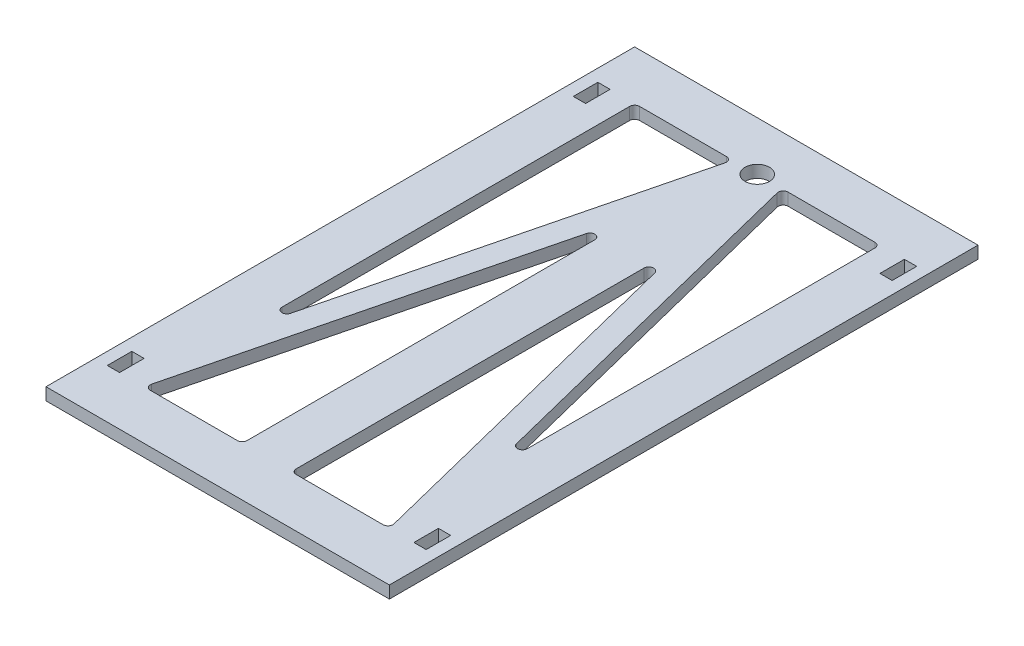
SolidWorks part; units mm, degrees
material "Beech"
ref_plane "Front Plane" through (0, 0, 0) normal (0, 0, 1) x (1, 0, 0)
ref_plane "Top Plane" through (0, 0, 0) normal (0, 1, 0) x (1, 0, 0)
ref_plane "Right Plane" through (0, 0, 0) normal (1, 0, 0) x (0, 0, -1)
sketch "Sketch1" plane through (0, 0, 0) normal (0, 1, 0) x (1, 0, 0)
  line L0 (0, 0) -> (177.8, 0)
  line L1 (0, 0) -> (0, 304.8)
  line L2 (177.8, 0) -> (177.8, 304.8)
  line L3 (0, 304.8) -> (177.8, 304.8)
  line L4 (0, 0) -> (12.7, 0)
  line L5 (0, 0) -> (0, -6.35)
  line L8 (177.8, 0) -> (165.1, 0)
  line L12 (127, 0) -> (114.3, 0)
  line L16 (50.8, 0) -> (63.5, 0)
  line L20 (165.1, 279.4) -> (171.45, 279.4)
  line L21 (165.1, 279.4) -> (165.1, 266.7)
  line L22 (171.45, 279.4) -> (171.45, 266.7)
  line L23 (165.1, 266.7) -> (171.45, 266.7)
  line L24 (6.35, 279.4) -> (12.7, 279.4)
  line L25 (6.35, 279.4) -> (6.35, 266.7)
  line L26 (12.7, 279.4) -> (12.7, 266.7)
  line L27 (6.35, 266.7) -> (12.7, 266.7)
  line L28 (6.35, 38.1) -> (12.7, 38.1)
  line L29 (6.35, 38.1) -> (6.35, 25.4)
  line L30 (12.7, 38.1) -> (12.7, 25.4)
  line L31 (6.35, 25.4) -> (12.7, 25.4)
  line L32 (165.1, 38.1) -> (171.45, 38.1)
  line L33 (165.1, 38.1) -> (165.1, 25.4)
  line L34 (171.45, 38.1) -> (171.45, 25.4)
  line L35 (165.1, 25.4) -> (171.45, 25.4)
  line L36 (101.6, 279.4) -> (152.4, 279.4)
  line L37 (152.4, 279.4) -> (152.4, 76.2)
  line L38 (152.4, 76.2) -> (101.6, 279.4)
  line L39 (101.6, 228.6) -> (101.6, 25.4)
  line L40 (101.6, 25.4) -> (152.4, 25.4)
  line L41 (152.4, 25.4) -> (101.6, 228.6)
  line L42 (76.2, 279.4) -> (25.4, 279.4)
  line L43 (25.4, 279.4) -> (25.4, 76.2)
  line L44 (25.4, 76.2) -> (76.2, 279.4)
  line L45 (76.2, 228.6) -> (76.2, 25.4)
  line L46 (76.2, 25.4) -> (25.4, 25.4)
  line L47 (25.4, 25.4) -> (76.2, 228.6)
  circle A0 centre (88.9, 279.4) radius 6.35
  point P21 (88.9, 304.8)
  dimension "D8" = 12.7
  dimension "D1" = 177.8
  dimension "D6" = 304.8
  dimension "D7" = 25.4
  dimension "D9" = 25.4
  dimension "D10" = 25.4
  dimension "D11" = 12.7
  dimension "D12" = 12.7
  dimension "D13" = 203.2
  dimension "D14" = 50.8
  dimension "D15" = 50.8
extrude "Front Panel" add sketch "Sketch1" along normal blind 6.35 contours L3 L1 L0 L2 A0 L35 L33 L32 L34 L31 L29 L28 L30 L27 L25 L24 L26 L23 L21 L20 L22 | L5 L0 | L0 | L0 | L0 region at (88.9, 0, -151.9139)
fillet "Fillet1" radius 2.54 12 edges at (25.4, 3.175, -76.2) (152.4, 3.175, -76.2) (25.4, 3.175, -25.4) (76.2, 3.175, -25.4) (101.6, 3.175, -25.4) (152.4, 3.175, -25.4) (76.2, 3.175, -228.6) (101.6, 3.175, -228.6) (25.4, 3.175, -279.4) (76.2, 3.175, -279.4) (101.6, 3.175, -279.4) (152.4, 3.175, -279.4)
equation "\"CageLeftBottomEdge\"=22.11mm"
equation "\"CageLeftTopEdge\"=22.11mm"
equation "\"CageRightBottomEdge\"=21.63mm"
equation "\"CageRightTopEdge\"=21.63mm"
equation "\"CageHeight\"=86.04mm"
equation "\"CageLength\"=73.76mm"
equation "\"CageTopScrewClearance\"=10mm"
equation "\"CageBottomScrewClearance\"=25mm"
equation "\"CageLeftTopDepth\"= 11.65mm"
equation "\"CageLeftBottomDepth\"=11.11mm"
equation "\"CageLeftTopHeight\"=8.56175mm"
equation "\"CageLeftBottomHeight\"=16mm"
equation "\"CageRightTopDepth\"= 11.05mm"
equation "\"CageRightBottomDepth\"=10.58mm"
equation "\"CageRightTopHeight\"=9.6mm"
equation "\"CageRightBottomHeight\"=15.49mm"
equation "\"CageLeftTopChannelDepth\"=2.41908mm"
equation "\"CageLeftBottomChannelDepth\"=2.588mm"
equation "\"CageLeftChannelHeight\"=11.7mm"
equation "\"CageRightTopChannelDepth\"=2.32mm"
equation "\"CageRightBottomChannelDepth\"=2.318mm"
equation "\"CageRightChannelHeight\"=10mm"
equation "\"CageChanRelHeight\"=23.99mm"
equation "\"CageChanRelDepth\"=5.492mm"
equation "\"CageChamberRadius\"=16.261mm"
equation "\"CageScrewDiameter\"=4.8mm"
equation "\"CageSetScrewDiameter\"=3.5mm"
equation "\"CageAxleRadius\"=6.639mm"
equation "\"CageAxleKeyHeight\"=1.619mm"
equation "\"CageAxleKeyWidth\"=2.662mm"
equation "\"CageHoseWindowWidth\"=16.29mm"
equation "\"CageHoseWindowHeight\"=26.5mm"
equation "\"CageHoseWindow-Edge\"=8.89mm"
equation "\"CageScrew-VerticalEdge\"=5.0mm"
equation "\"CageScrew-HorizontalEdge\"=7.5mm"
equation "\"CageScrew-HoseCornerScrewEdge\"=4.45mm"
equation "\"CageAxle-BottomEdge\"=56.05mm"
equation "\"CageAxle-FrontEdge\"=46.03mm"
equation "\"CageBackSetScrew-Axle\"=40mm"
equation "\"CageFrontSetScrew-Axle\"=22mm"
equation "\"CageVelocityWindow-BackEdge\"=34.8mm"
equation "\"CageVelocityWindow-BottomEdge\"=27.55mm"
equation "\"CageVelocityWindowHeight\"=22.29mm"
equation "\"CageVelocityWindowWidth\"=12.61mm"
equation "\"TriggerSlot-BottomEdge\"=6.35mm"
equation "\"TriggerSlot-FrontEdge\"=15mm"
equation "\"TriggerSlotSize\"=6.7mm"
equation "\"TriggerRackOffset\"=6mm"
equation "\"TriggerSlotSizeInt\"=.25in"
equation "\"MotorMountLegLength\"=.25in"
equation "\"GearOffset\"=.264907in"
equation "\"TriggerSlotSpacing\"=.25in"
equation "\"TriggerMiniSlotWidth\"=3.5mm"
equation "\"TriggerRackWidth\"=6.5mm"
equation "\"pandiscradius\"=14in"
equation "\"towermaterialwidth\"=.25in"
equation "\"towerslotlength\"=.5in"
equation "\"towermarkerspace\"=5in"
equation "\"towerslothorizoffset\"=1in"
equation "\"towerslothorizspacing\"=2in"
equation "\"towerslotvertoffset\"=3in"
equation "\"towerslotvertspacing\"=1in"
equation "\"towerheight\"=12in"
equation "\"towerupslot\"=1in"
equation "\"D1@Sketch1\"=(\"towerslothorizoffset\"+\"towerslothorizspacing\"+\"towerslotlength\")*2"
equation "\"D2@Sketch1\"=\"towermaterialwidth\""
equation "\"D3@Sketch1\"=\"towerslotlength\""
equation "\"D4@Sketch1\"=\"towerslothorizspacing\""
equation "\"D5@Sketch1\"=\"towerslothorizspacing\""
equation "\"D6@Sketch1\"=\"towerheight\""
equation "\"D7@Sketch1\"=\"towerupslot\""
equation "\"toweraxle\"=.5in"
equation "\"D8@Sketch1\"=\"toweraxle\""
equation "\"D9@Sketch1\"=\"towerupslot\""
equation "\"D10@Sketch1\"= \"towerupslot\""
equation "\"D1@Front Panel\"=\"towermaterialwidth\""
equation "\"stepperouterrad\"=10mm"
equation "\"stepperscrewsize\"=3.45mm"
equation "\"stepperscrewc2c\"=49.5mm"
equation "\"stepperdepthoffset\"=24mm"
equation "\"stepperhorizoffset\"=22.91mm"
equation "\"shaftslotOD\"=18.8mm"
equation "\"shaftslotID\"=13.28mm"
equation "\"shaftkeywidth\"=2.67mm"
equation "\"shaftkeydepth\"=1.8mm"
equation "\"shaftcollartotaldepth\"=9.71mm"
equation "\"shaftsquaredepth\"=6mm"
equation "\"shaftsetscrewsize\"=3.5mm"
equation "\"shaftkeytightdepth\"=1.85mm"
equation "\"shaftslottightID\"=12.78mm"
equation "\"shaftsetscrewoffset\"=9mm"
equation "\"cagecollartotaldepth\"=10mm"
equation "\"cagecollartotalwidth\"=35mm"
equation "\"cagecollarbasedepth\"=4mm"
equation "\"D11@Sketch1\"=\"toweraxle\""
equation "\"D12@Sketch1\"=\"toweraxle\""
equation "\"towerspeedwidth\"=2in"
equation "\"D15@Sketch1\"=\"towerspeedwidth\""
equation "\"towerspeedheight\"=8in"
equation "\"D13@Sketch1\"=\"towerspeedheight\""
equation "\"towerspeedgap\"=2in"
equation "\"D14@Sketch1\"=\"towerspeedgap\""
equation "\"gearhubintdiam\"=30mm"
equation "\"gearhubintwid\"=12.21mm"
equation "\"stepperaxleflat\"=.037in"
equation "\"stepperaxlerad\"=0.11811024in"
equation "\"ajaxaxlesize\"=3.87mm"
equation "\"ajaxinnercut\"=2.3mm"
equation "\"ajaxwidth\"=6.1mm"
equation "\"ajaxdiametral\"=25.8854"
equation "\"ajaxcutoutdepth\"=2.3mm"
equation "\"ajax4020gap\"=29.5mm"
equation "\"ajax4010gap\"=24.5mm"
equation "\"ajax20hubbuffer\"=6.1mm"
equation "\"ajax20hubholeoffset\"=.19685in"
equation "\"ajax20hubholesize\"=.059055in"
equation "\"ajax20cutoutint\"=13.4mm"
equation "\"ajax40hubholesize\"=7.21mm"
equation "\"ajax40hubholeoffset\"=10mm"
equation "\"ajax40hubbuffer\"=8.9mm"
equation "\"ajax40cutoutint\"=32.6mm"
equation "\"bearingpandiscrad\"=6.8in"
equation "\"bearingpandiscang\"=48.75deg"
equation "\"bearingclearholedist\"=4.7345in"
equation "\"bearingclearholesize\"=.5in"
equation "\"bearingclearholeang\"=22.5deg"
equation "\"bearingmountholedist\"=4.25in"
equation "\"bearingwirehole\"=1.5in"
equation "\"no6diam\"=.146in"
equation "\"shortconangle\"=20deg"
equation "\"shortconlen\"=.875in"
equation "\"longconlen\"=1.25in"
equation "\"longconangle\"=15deg"
